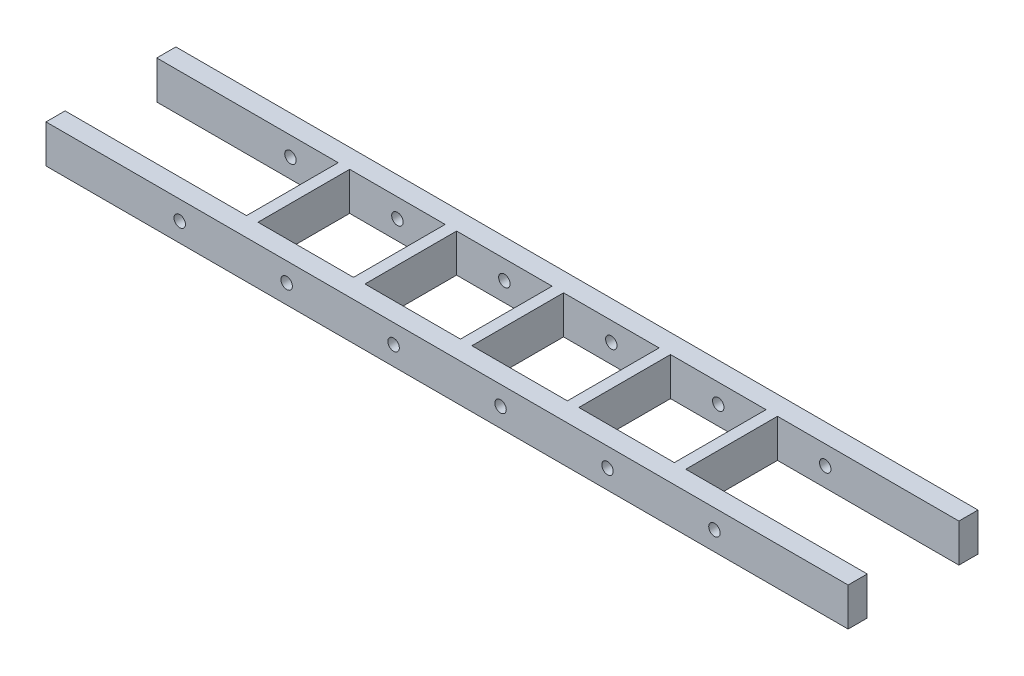
SolidWorks part; units mm, degrees
ref_plane "前视基准面" through (0, 0, 0) normal (0, 0, 1) x (1, 0, 0)
ref_plane "上视基准面" through (0, 0, 0) normal (0, 1, 0) x (1, 0, 0)
ref_plane "右视基准面" through (0, 0, 0) normal (1, 0, 0) x (0, 0, -1)
other "Configuration Table"
sketch "草图1" plane through (0, 0, 0) normal (0, 0, 1) x (1, 0, 0)
  line L0 (-100, 0) -> (100, 0) construction
  line L1 (-105, -5) -> (105, -5)
  line L2 (-105, -5) -> (-105, 5)
  line L3 (-105, 5) -> (105, 5)
  line L4 (105, -5) -> (105, 5)
  line L5 (-105, -5) -> (105, 5) construction
  line L6 (-105, 5) -> (105, -5) construction
  line L7 (0, 24.0554) -> (0, -52.1273) construction
  line L8 (-100, -40.1628) -> (0, -40.1628) construction
  line L9 (0, -40.1628) -> (100, -40.1628) construction
  line L10 (-50, -40.1628) -> (-50, -63.9624) construction
  line L11 (50, -40.1628) -> (50, -63.9624) construction
  line L12 (-50, -58.5361) -> (-100, -58.5361) construction
  line L13 (-50, -58.5361) -> (0, -58.5361) construction
  line L14 (0, -58.5361) -> (50, -58.5361) construction
  line L15 (50, -58.5361) -> (100, -58.5361) construction
  line L16 (-75, -58.5361) -> (-75, -63.9624) construction
  line L17 (-25, -58.5361) -> (-25, -63.9624) construction
  line L18 (25, -58.5361) -> (25, -63.9624) construction
  line L19 (75, -58.5361) -> (75, -63.9624) construction
  line L20 (-70, 0) -> (-42, 0)
  line L21 (-42, 0) -> (-14, 0)
  line L22 (-14, 0) -> (14, 0)
  line L24 (14, 0) -> (42, 0)
  line L25 (70, 0) -> (42, 0)
  line L26 (-57.5, -5) -> (-54.5, -5)
  line L27 (-57.5, -5) -> (-57.5, 5)
  line L28 (-57.5, 5) -> (-54.5, 5)
  line L29 (-54.5, -5) -> (-54.5, 5)
  line L30 (-57.5, -5) -> (-54.5, 5) construction
  line L31 (-57.5, 5) -> (-54.5, -5) construction
  line L32 (-29.5, -5) -> (-26.5, -5)
  line L33 (-29.5, -5) -> (-29.5, 5)
  line L34 (-29.5, 5) -> (-26.5, 5)
  line L35 (-26.5, -5) -> (-26.5, 5)
  line L36 (-29.5, -5) -> (-26.5, 5) construction
  line L37 (-29.5, 5) -> (-26.5, -5) construction
  line L38 (-1.5, -5) -> (1.5, -5)
  line L39 (-1.5, -5) -> (-1.5, 5)
  line L40 (-1.5, 5) -> (1.5, 5)
  line L41 (1.5, -5) -> (1.5, 5)
  line L42 (-1.5, -5) -> (1.5, 5) construction
  line L43 (-1.5, 5) -> (1.5, -5) construction
  line L44 (26.5, -5) -> (29.5, -5)
  line L45 (26.5, -5) -> (26.5, 5)
  line L46 (26.5, 5) -> (29.5, 5)
  line L47 (29.5, -5) -> (29.5, 5)
  line L48 (26.5, -5) -> (29.5, 5) construction
  line L49 (26.5, 5) -> (29.5, -5) construction
  line L50 (54.5, -5) -> (57.5, -5)
  line L51 (54.5, -5) -> (54.5, 5)
  line L52 (54.5, 5) -> (57.5, 5)
  line L53 (57.5, -5) -> (57.5, 5)
  line L54 (54.5, -5) -> (57.5, 5) construction
  line L55 (54.5, 5) -> (57.5, -5) construction
  circle A0 centre (-70, 0) radius 1.5
  circle A1 centre (-42, 0) radius 1.5
  circle A2 centre (-14, 0) radius 1.5
  circle A3 centre (14, 0) radius 1.5
  circle A4 centre (42, 0) radius 1.5
  circle A5 centre (70, 0) radius 1.5
  point P0 (0, 0)
  point P42 (-56, 0)
  point P47 (-28, 0)
  point P52 (0, 0)
  point P57 (28, 0)
  point P62 (56, 0)
  dimension "D4" = 3
  dimension "D1" = 200
  dimension "D2" = 5
  dimension "D3" = 10
  dimension "D5" = 14
  dimension "D6" = 14
  dimension "D7" = 3
extrude "凸台-拉伸1" add sketch "草图1" along normal blind 5 contours L3 L4 L1 L2 | A0 | A1 | A2 | A3 | A4 | A5
ref_plane "基准面1" through (0, 0, 29) normal (0, 0, 1) x (1, 0, 0)
extrude "凸台-拉伸2" add sketch "草图1<3>" along normal blind 5 from surface separate body contours L3 L4 L1 L2 | A5 | A3 | A2 | A0 | A1 | A4 starting at plane "基准面1"
sketch "草图1<3>" plane through (0, 0, 0) normal (0, 0, 1) x (1, 0, 0) same geometry as "草图1"
extrude "凸台-拉伸3" add sketch "草图1<4>" along normal up to surface (29 mm away) contours L27 L28 L29 L26 | L33 L34 L35 L32 | L39 L40 L41 L38 | L45 L46 L47 L44 | L51 L52 L53 L50 up to face at (-40.5, 0, 29)
sketch "草图1<4>" plane through (0, 0, 0) normal (0, 0, 1) x (1, 0, 0) same geometry as "草图1"
